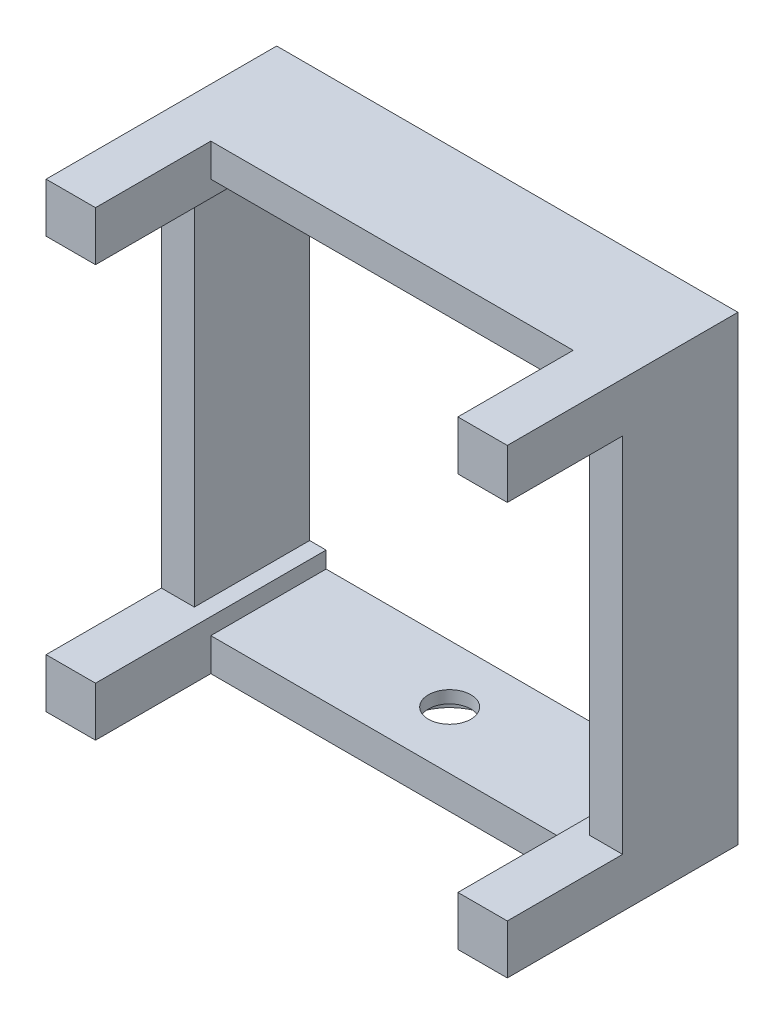
SolidWorks part; units mm, degrees
ref_plane "Alzado" through (0, 0, 0) normal (0, 0, 1) x (1, 0, 0)
ref_plane "Planta" through (0, 0, 0) normal (0, 1, 0) x (1, 0, 0)
ref_plane "Vista lateral" through (0, 0, 0) normal (1, 0, 0) x (0, 0, -1)
sketch "Croquis1" plane through (0, 0, 0) normal (0, 0, 1) x (1, 0, 0)
  line L0 (-15.5, -15.5) -> (-15.5, 80.5)
  line L4 (-15.5, 80.5) -> (80.5, 80.5)
  line L5 (80.5, -15.5) -> (80.5, 80.5)
  line L6 (0, 0) -> (65, 0)
  line L7 (0, 0) -> (0, 65)
  line L8 (0, 65) -> (65, 65)
  line L9 (65, 0) -> (65, 65)
  line L18 (-15.5, -15.5) -> (80.5, -15.5)
  line L19 (-23.5, -23.5) -> (88.5, -23.5)
  line L20 (88.5, -23.5) -> (88.5, 88.5)
  line L21 (-23.5, 88.5) -> (88.5, 88.5)
  line L22 (-23.5, -23.5) -> (-23.5, 88.5)
  dimension "D1" = 15.5
  dimension "D2" = 8
extrude "Saliente-Extruir2" add sketch "Croquis1" against normal blind 28 contours L22 L19 L20 L21 L18 L0 L4 L5 region at (-21.9161, 32.5, 0)
sketch "Croquis2" plane through (0, -23.5, 0) normal (0, -1, 0) x (1, 0, 0)
  line L0 (-23.5, -14) -> (88.5, -14) construction
  line L1 (-23.5, -28) -> (-23.5, 0) construction
  line L2 (88.5, -28) -> (88.5, 0) construction
  circle A0 centre (32.5, -14) radius 5.155
extrude "Cortar-Extruir1" cut sketch "Croquis2" against normal blind 8
sketch "Croquis3" plane through (0, -23.5, 0) normal (0, -1, 0) x (1, 0, 0)
  line L0 (-23.5, -14) -> (88.5, -14) construction
  line L1 (-23.5, -28) -> (-23.5, 0) construction
  line L2 (88.5, -28) -> (88.5, 0) construction
  circle A0 centre (32.5, -14) radius 11.115
extrude "Cortar-Extruir2" cut sketch "Croquis3" against normal blind 5
sketch "Croquis4" plane through (0, 80.5, 0) normal (0, -1, 0) x (1, 0, 0)
  line L0 (-15.5, -14) -> (80.5, -14) construction
  line L1 (-15.5, -28) -> (-15.5, 0) construction
  line L2 (80.5, -28) -> (80.5, 0) construction
  circle A0 centre (32.5, -14) radius 6.5
extrude "Cortar-Extruir3" cut sketch "Croquis4" against normal blind 5
sketch "Croquis5" plane through (0, 0, 0) normal (0, 0, 1) x (1, 0, 0)
  line L1 (-23.5, 88.5) -> (-11.5, 88.5)
  line L2 (-23.5, 88.5) -> (-23.5, 76.5)
  line L3 (-23.5, 76.5) -> (-11.5, 76.5)
  line L4 (-11.5, 88.5) -> (-11.5, 76.5)
  line L5 (-23.5, -23.5) -> (-11.5, -23.5)
  line L6 (-23.5, -23.5) -> (-23.5, -11.5)
  line L7 (-23.5, -11.5) -> (-11.5, -11.5)
  line L8 (-11.5, -23.5) -> (-11.5, -11.5)
  line L9 (88.5, -23.5) -> (76.5, -23.5)
  line L10 (88.5, -23.5) -> (88.5, -11.5)
  line L11 (88.5, -11.5) -> (76.5, -11.5)
  line L12 (76.5, -23.5) -> (76.5, -11.5)
  line L13 (88.5, 88.5) -> (76.5, 88.5)
  line L14 (88.5, 88.5) -> (88.5, 76.5)
  line L15 (88.5, 76.5) -> (76.5, 76.5)
  line L16 (76.5, 88.5) -> (76.5, 76.5)
  dimension "D1" = 12
  dimension "D2" = 12
  dimension "D3" = 12
  dimension "D4" = 12
  dimension "D5" = 12
  dimension "D6" = 12
  dimension "D7" = 12
  dimension "D8" = 12
extrude "Saliente-Extruir3" add sketch "Croquis5" along normal blind 28 and the other way blind 28
